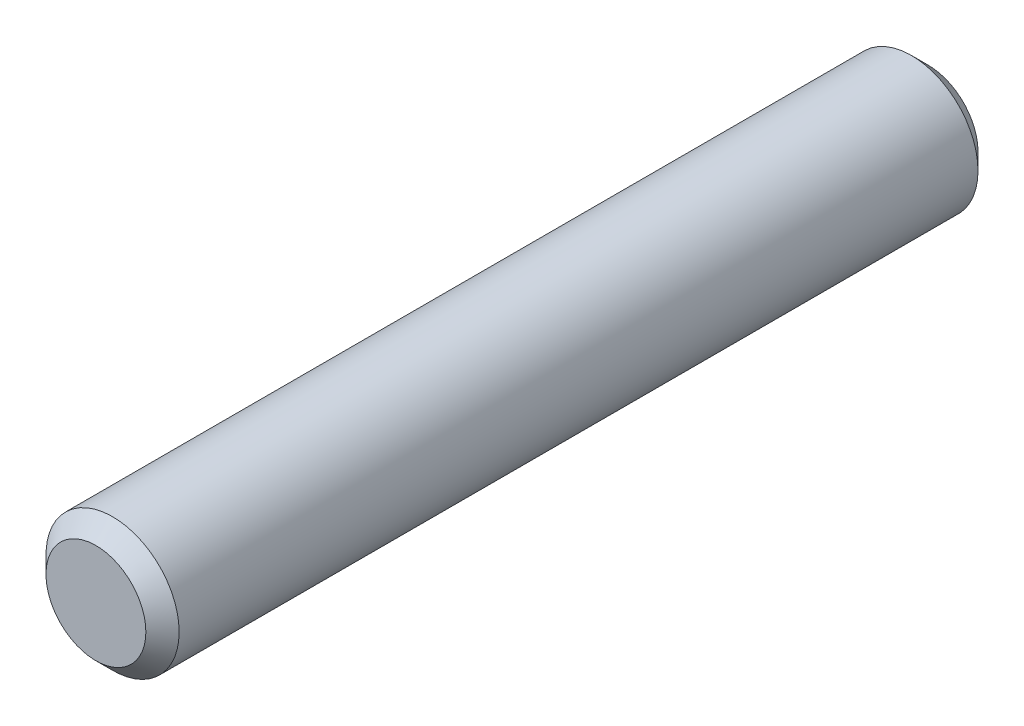
SolidWorks part; units mm, degrees
other "Папка сварных швов"
material "Ст 3 ГОСТ 380-88"
ref_plane "Front" through (0, 0, 0) normal (0, 0, 1) x (1, 0, 0)
ref_plane "Top" through (0, 0, 0) normal (0, 1, 0) x (1, 0, 0)
ref_plane "Right" through (0, 0, 0) normal (1, 0, 0) x (0, 0, -1)
sketch "Sketch1" plane through (0, 0, 0) normal (0, 0, 1) x (1, 0, 0)
  circle A0 centre (0, 0) radius 4
  point P4 (0, 0)
  dimension "D1" = 8
extrude "Boss-Extrude1" add sketch "Sketch1" along normal blind 50
ref_axis "Axis1" through (0, 0, 50) along (0, 0, -1)
ref_plane "Plane1" through (0, 0, 30) normal (0, 0, 1) x (1, 0, 0)
sketch "Sketch2" plane through (0, 0, 30) normal (0, 0, 1) x (1, 0, 0)
  point P0 (0, 0)
sketch "Sketch3" plane through (0, 0, 0) normal (1, 0, 0) x (0, 0, -1)
  line L0 (-30, 0) -> (-53.8019, 0) construction
chamfer "Chamfer1" distance 1 angle 45 2 edges at (4, 0, 0) (4, 0, 50)
